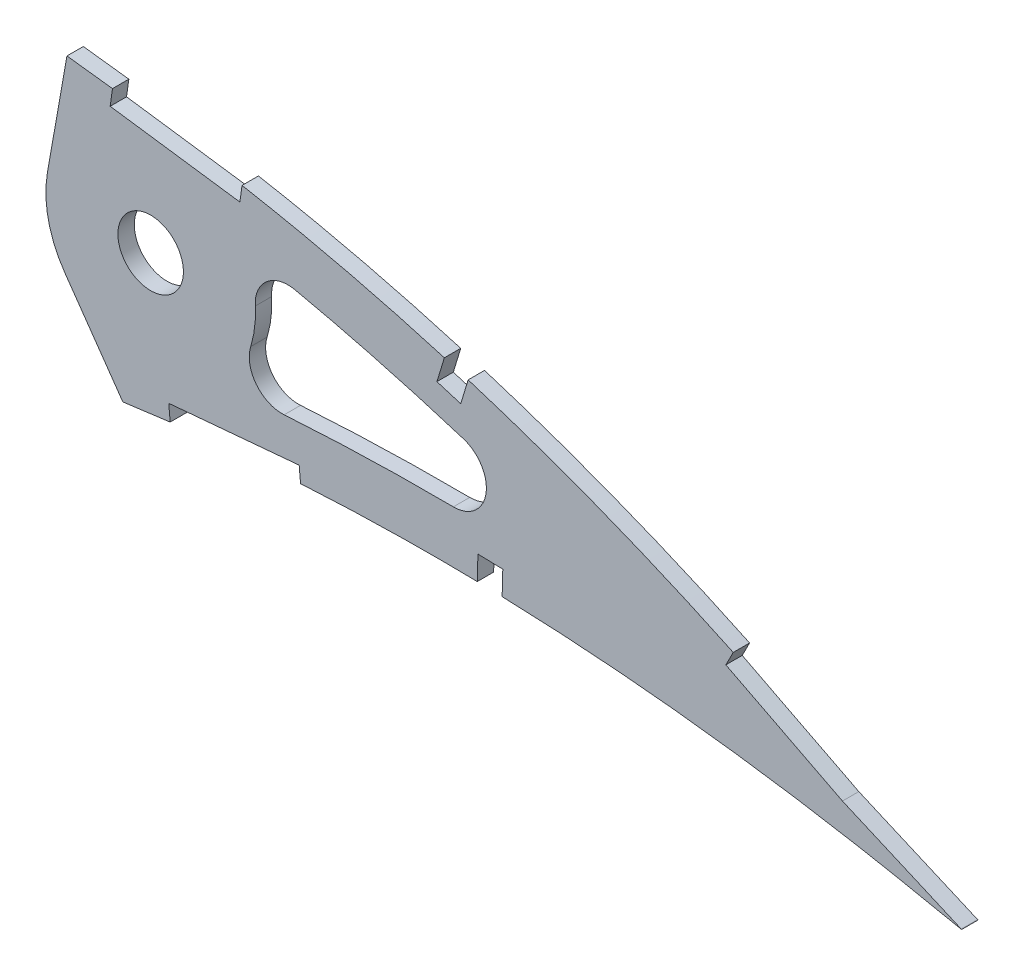
SolidWorks part; units mm, degrees
material "Pine"
ref_plane "Front Plane" through (0, 0, 0) normal (0, 0, 1) x (1, 0, 0)
ref_plane "Top Plane" through (0, 0, 0) normal (0, 1, 0) x (1, 0, 0)
ref_plane "Right Plane" through (0, 0, 0) normal (1, 0, 0) x (0, 0, -1)
curve "Curve2"
curve "Curve3"
sketch "Sketch1" plane through (0, 0, 0) normal (0, 0, 1) x (1, 0, 0)
  line L1 (519.5802, -0.8111) -> (524.4049, -1.7687)
  line L2 (520.229, 0.8111) -> (524.4049, -1.7687)
  spline S0 degree 3 poles (-2903.7635, -749.124) (66.2436, 68.8235) (-8.6937, 20.855) (1.129, -3.7148) (2.0912, -5.4642) (3.3081, -7.1386) (4.7718, -8.7374) (6.479, -10.2623) (8.428, -11.7125) (10.6162, -13.0874) (13.0406, -14.3883) (15.6982, -15.6145) (18.5868, -16.7656) (21.7032, -17.8401) (25.0435, -18.8396) (28.6046, -19.7616) (32.3825, -20.6074) (36.3735, -21.375) (40.5732, -22.065) (44.9774, -22.6771) (49.5814, -23.2117) (54.3808, -23.6676) (59.3708, -24.0458) (64.5464, -24.3466) (69.9027, -24.5709) (75.4344, -24.718) (81.1363, -24.7899) (87.003, -24.788) (93.0289, -24.7115) (99.2088, -24.5648) (105.5368, -24.3469) (112.0073, -24.0604) (118.6142, -23.7083) (125.3518, -23.2917) (132.2141, -22.8125) (139.1951, -22.2745) (146.2885, -21.679) (153.4882, -21.0296) (160.7876, -20.3295) (168.1806, -19.5808) (175.6606, -18.7872) (183.2209, -17.9512) (190.8551, -17.0772) (198.5563, -16.1668) (206.3179, -15.2253) (214.1326, -14.2544) (221.9939, -13.2579) (229.8947, -12.2404) (237.8276, -11.2019) (245.786, -10.1497) (253.7621, -9.0829) (261.7491, -8.0072) (269.7395, -6.9257) (277.7256, -5.8389) (285.7003, -4.7513) (293.6562, -3.6657) (301.5856, -2.5824) (309.4812, -1.5067) (317.3352, -0.4385) (325.1402, 0.6201) (332.8888, 1.6659) (340.5737, 2.6975) (348.187, 3.7144) (355.721, 4.7168) (363.0553, 5.6745) (370.1707, 6.6383) (377.0913, 7.4284) (383.9258, 8.1028) (390.6811, 8.6557) (397.3493, 9.0951) (403.9227, 9.4241) (410.3934, 9.6473) (416.7532, 9.7713) (422.9943, 9.7993) (429.1081, 9.7402) (435.0867, 9.5987) (440.9216, 9.3813) (446.6049, 9.0952) (452.1283, 8.7483) (457.4837, 8.3456) (462.6634, 7.8966) (467.6597, 7.4078) (472.4647, 6.8849) (477.0715, 6.3387) (481.4727, 5.7729) (485.6616, 5.1968) (489.6316, 4.6162) (493.3764, 4.0385) (496.89, 3.4693) (500.1667, 2.916) (503.2016, 2.384) (505.9892, 1.8782) (508.5257, 1.4052) (510.8062, 0.9673) (512.8275, 0.5717) (514.5859, 0.2202) (516.0789, -0.0824) (517.3037, -0.3347) (518.2586, -0.5328) (518.9417, -0.6767) (537.0698, -4.4604) (553.3394, -15.9066) (1193.1482, 2921.6684) knots -0.137857 -0.137857 -0.137857 -0.137857 0.003638 0.007293 0.011028 0.014901 0.018963 0.023258 0.027821 0.032679 0.037853 0.043362 0.049215 0.055422 0.061989 0.068918 0.076211 0.083868 0.091887 0.100266 0.109 0.118085 0.127515 0.137285 0.147388 0.157816 0.168563 0.179619 0.190977 0.202627 0.21456 0.226767 0.239236 0.251959 0.264924 0.27812 0.291536 0.30516 0.318981 0.332985 0.347163 0.361499 0.375981 0.390597 0.405333 0.420175 0.43511 0.450124 0.465203 0.480333 0.495501 0.51069 0.525887 0.541078 0.556247 0.571382 0.586466 0.601485 0.616424 0.631269 0.646007 0.660621 0.675098 0.689423 0.703582 0.716908 0.730009 0.742952 0.755726 0.76832 0.780724 0.792927 0.804916 0.816679 0.828204 0.839475 0.850481 0.861208 0.871639 0.881763 0.891564 0.901027 0.910139 0.918884 0.927249 0.935221 0.942785 0.949928 0.956638 0.962904 0.968712 0.974054 0.978918 0.983297 0.98718 0.990561 0.993433 0.995791 0.99763 0.998946 0.999737 1.102307 1.102307 1.102307 1.102307 only from (0, 0) to (519.5802, -0.8111) construction
  spline S1 degree 3 poles (2144.5607, 2521.6799) (550.9976, -26.3511) (537.2872, -9.6513) (519.6711, 1.1542) (519.0735, 1.5208) (518.237, 2.0313) (517.1622, 2.6844) (515.8486, 3.4756) (514.2969, 4.4021) (512.5075, 5.4598) (510.4807, 6.6436) (508.2172, 7.9486) (505.7172, 9.3676) (502.9816, 10.8948) (500.0114, 12.5227) (496.8072, 14.2443) (493.3701, 16.0505) (489.7015, 17.9338) (485.8019, 19.8836) (481.6733, 21.8919) (477.317, 23.9487) (472.7345, 26.0429) (467.9284, 28.1661) (462.9001, 30.305) (457.6524, 32.4505) (452.1876, 34.5902) (446.5089, 36.7144) (440.6184, 38.8094) (434.5207, 40.866) (428.2186, 42.8708) (421.7166, 44.813) (415.0186, 46.68) (408.1302, 48.4622) (401.0555, 50.1466) (393.8008, 51.7219) (386.3718, 53.1787) (378.7746, 54.5024) (371.0303, 55.692) (363.2636, 56.6815) (355.5128, 57.652) (347.7736, 58.5637) (339.9398, 59.4368) (332.019, 60.2663) (324.019, 61.0497) (315.9478, 61.7836) (307.814, 62.4658) (299.6253, 63.0925) (291.3904, 63.6628) (283.1174, 64.1714) (274.8152, 64.6183) (266.4922, 65.0001) (258.157, 65.3142) (249.8185, 65.5589) (241.4854, 65.7316) (233.1666, 65.8314) (224.8708, 65.8555) (216.6071, 65.8035) (208.384, 65.6736) (200.2107, 65.464) (192.0958, 65.1743) (184.048, 64.8046) (176.0762, 64.3519) (168.189, 63.8191) (160.3952, 63.2038) (152.7034, 62.506) (145.1216, 61.7286) (137.6583, 60.8693) (130.3214, 59.9308) (123.1191, 58.9147) (116.0593, 57.8206) (109.1496, 56.6517) (102.3976, 55.409) (95.8102, 54.0963) (89.3948, 52.714) (83.1581, 51.266) (77.1065, 49.7551) (71.2467, 48.1838) (65.5845, 46.5561) (60.1256, 44.8756) (54.8764, 43.1442) (49.8409, 41.3683) (45.0253, 39.5493) (40.4333, 37.6928) (36.0702, 35.8014) (31.9393, 33.8806) (28.0452, 31.9329) (24.3908, 29.9636) (20.9797, 27.9757) (17.8153, 25.973) (14.8987, 23.9604) (12.2341, 21.9394) (9.8224, 19.9149) (7.6651, 17.8901) (5.7652, 15.8664) (4.1228, 13.8473) (2.7399, 11.8344) (1.6168, 9.8297) (0.7561, 7.8345) (0.1568, 5.85) (-0.1712, 3.8792) (-1.2714, -22.5145) (85.5395, -42.7616) (-2987.8188, -259.5241) knots -0.109813 -0.109813 -0.109813 -0.109813 0.000254 0.001015 0.002283 0.004057 0.006331 0.009105 0.012374 0.016134 0.02038 0.025106 0.030306 0.035972 0.0421 0.048678 0.055702 0.06316 0.071046 0.07935 0.088063 0.097176 0.106678 0.116562 0.126814 0.137428 0.148394 0.1597 0.171338 0.183298 0.19557 0.208144 0.221012 0.234162 0.247587 0.261277 0.275223 0.289414 0.303771 0.317689 0.331784 0.34604 0.360444 0.374983 0.38964 0.404403 0.419257 0.434187 0.449177 0.464215 0.479284 0.49437 0.509458 0.524532 0.539579 0.554583 0.56953 0.584403 0.599191 0.613877 0.628447 0.642889 0.657186 0.671326 0.685294 0.699078 0.712665 0.726043 0.739198 0.752118 0.764792 0.777208 0.789356 0.801224 0.812804 0.824083 0.835055 0.84571 0.856038 0.866034 0.875689 0.884998 0.893953 0.902553 0.910789 0.918661 0.926166 0.933303 0.940071 0.946475 0.952518 0.958205 0.963547 0.968557 0.97325 0.977651 0.981787 0.985694 0.989415 0.993001 0.996508 1.132043 1.132043 1.132043 1.132043 only from (520.229, 0.8111) to (0, 0) construction
  spline S2 degree 3 poles (0, 0) (0.1336, -0.6306) (0.4014, -1.8948) (1.129, -3.7148) (2.0912, -5.4642) (3.3081, -7.1386) (4.7718, -8.7374) (6.479, -10.2623) (8.428, -11.7125) (10.6162, -13.0874) (13.0406, -14.3883) (15.6982, -15.6145) (18.5868, -16.7656) (21.7032, -17.8401) (25.0435, -18.8396) (28.6046, -19.7616) (32.3825, -20.6074) (36.3735, -21.375) (40.5732, -22.065) (44.9774, -22.6771) (49.5814, -23.2117) (54.3808, -23.6676) (59.3708, -24.0458) (64.5464, -24.3466) (69.9027, -24.5709) (75.4344, -24.718) (81.1363, -24.7899) (87.003, -24.788) (93.0289, -24.7115) (99.2088, -24.5648) (105.5368, -24.3469) (112.0073, -24.0604) (118.6142, -23.7083) (125.3518, -23.2917) (132.2141, -22.8125) (139.1951, -22.2745) (146.2885, -21.679) (153.4882, -21.0296) (160.7876, -20.3295) (168.1806, -19.5808) (175.6606, -18.7872) (183.2209, -17.9512) (190.8551, -17.0772) (198.5563, -16.1668) (206.3179, -15.2253) (214.1326, -14.2544) (221.9939, -13.2579) (229.8947, -12.2404) (237.8276, -11.2019) (245.786, -10.1497) (253.7621, -9.0829) (261.7491, -8.0072) (269.7395, -6.9257) (277.7256, -5.8389) (285.7003, -4.7513) (293.6562, -3.6657) (301.5856, -2.5824) (309.4812, -1.5067) (317.3352, -0.4385) (325.1402, 0.6201) (332.8888, 1.6659) (340.5737, 2.6975) (348.187, 3.7144) (355.721, 4.7168) (363.0553, 5.6745) (370.1707, 6.6383) (377.0913, 7.4284) (383.9258, 8.1028) (390.6811, 8.6557) (397.3493, 9.0951) (403.9227, 9.4241) (410.3934, 9.6473) (416.7532, 9.7713) (422.9943, 9.7993) (429.1081, 9.7402) (435.0867, 9.5987) (440.9216, 9.3813) (446.6049, 9.0952) (452.1283, 8.7483) (457.4837, 8.3456) (462.6634, 7.8966) (467.6597, 7.4078) (472.4647, 6.8849) (477.0715, 6.3387) (481.4727, 5.7729) (485.6616, 5.1968) (489.6316, 4.6162) (493.3764, 4.0385) (496.89, 3.4693) (500.1667, 2.916) (503.2016, 2.384) (505.9892, 1.8782) (508.5257, 1.4052) (510.8062, 0.9673) (512.8275, 0.5717) (514.5859, 0.2202) (516.0789, -0.0824) (517.3037, -0.3347) (518.2586, -0.5328) (518.9417, -0.6767) (519.3522, -0.7624) (519.5346, -0.8013) (519.5802, -0.8111) knots 0 0 0 0 0.003638 0.007293 0.011028 0.014901 0.018963 0.023258 0.027821 0.032679 0.037853 0.043362 0.049215 0.055422 0.061989 0.068918 0.076211 0.083868 0.091887 0.100266 0.109 0.118085 0.127515 0.137285 0.147388 0.157816 0.168563 0.179619 0.190977 0.202627 0.21456 0.226767 0.239236 0.251959 0.264924 0.27812 0.291536 0.30516 0.318981 0.332985 0.347163 0.361499 0.375981 0.390597 0.405333 0.420175 0.43511 0.450124 0.465203 0.480333 0.495501 0.51069 0.525887 0.541078 0.556247 0.571382 0.586466 0.601485 0.616424 0.631269 0.646007 0.660621 0.675098 0.689423 0.703582 0.716908 0.730009 0.742952 0.755726 0.76832 0.780724 0.792927 0.804916 0.816679 0.828204 0.839475 0.850481 0.861208 0.871639 0.881763 0.891564 0.901027 0.910139 0.918884 0.927249 0.935221 0.942785 0.949928 0.956638 0.962904 0.968712 0.974054 0.978918 0.983297 0.98718 0.990561 0.993433 0.995791 0.99763 0.998946 0.999737 1 1 1 1
  spline S3 degree 3 poles (520.229, 0.8111) (520.1892, 0.8357) (520.0299, 0.9341) (519.6711, 1.1542) (519.0735, 1.5208) (518.237, 2.0313) (517.1622, 2.6844) (515.8486, 3.4756) (514.2969, 4.4021) (512.5075, 5.4598) (510.4807, 6.6436) (508.2172, 7.9486) (505.7172, 9.3676) (502.9816, 10.8948) (500.0114, 12.5227) (496.8072, 14.2443) (493.3701, 16.0505) (489.7015, 17.9338) (485.8019, 19.8836) (481.6733, 21.8919) (477.317, 23.9487) (472.7345, 26.0429) (467.9284, 28.1661) (462.9001, 30.305) (457.6524, 32.4505) (452.1876, 34.5902) (446.5089, 36.7144) (440.6184, 38.8094) (434.5207, 40.866) (428.2186, 42.8708) (421.7166, 44.813) (415.0186, 46.68) (408.1302, 48.4622) (401.0555, 50.1466) (393.8008, 51.7219) (386.3718, 53.1787) (378.7746, 54.5024) (371.0303, 55.692) (363.2636, 56.6815) (355.5128, 57.652) (347.7736, 58.5637) (339.9398, 59.4368) (332.019, 60.2663) (324.019, 61.0497) (315.9478, 61.7836) (307.814, 62.4658) (299.6253, 63.0925) (291.3904, 63.6628) (283.1174, 64.1714) (274.8152, 64.6183) (266.4922, 65.0001) (258.157, 65.3142) (249.8185, 65.5589) (241.4854, 65.7316) (233.1666, 65.8314) (224.8708, 65.8555) (216.6071, 65.8035) (208.384, 65.6736) (200.2107, 65.464) (192.0958, 65.1743) (184.048, 64.8046) (176.0762, 64.3519) (168.189, 63.8191) (160.3952, 63.2038) (152.7034, 62.506) (145.1216, 61.7286) (137.6583, 60.8693) (130.3214, 59.9308) (123.1191, 58.9147) (116.0593, 57.8206) (109.1496, 56.6517) (102.3976, 55.409) (95.8102, 54.0963) (89.3948, 52.714) (83.1581, 51.266) (77.1065, 49.7551) (71.2467, 48.1838) (65.5845, 46.5561) (60.1256, 44.8756) (54.8764, 43.1442) (49.8409, 41.3683) (45.0253, 39.5493) (40.4333, 37.6928) (36.0702, 35.8014) (31.9393, 33.8806) (28.0452, 31.9329) (24.3908, 29.9636) (20.9797, 27.9757) (17.8153, 25.973) (14.8987, 23.9604) (12.2341, 21.9394) (9.8224, 19.9149) (7.6651, 17.8901) (5.7652, 15.8664) (4.1228, 13.8473) (2.7399, 11.8344) (1.6168, 9.8297) (0.7561, 7.8345) (0.1568, 5.85) (-0.1712, 3.8792) (-0.2528, 1.9205) (-0.0842, 0.6392) (0, 0) knots 0 0 0 0 0.000254 0.001015 0.002283 0.004057 0.006331 0.009105 0.012374 0.016134 0.02038 0.025106 0.030306 0.035972 0.0421 0.048678 0.055702 0.06316 0.071046 0.07935 0.088063 0.097176 0.106678 0.116562 0.126814 0.137428 0.148394 0.1597 0.171338 0.183298 0.19557 0.208144 0.221012 0.234162 0.247587 0.261277 0.275223 0.289414 0.303771 0.317689 0.331784 0.34604 0.360444 0.374983 0.38964 0.404403 0.419257 0.434187 0.449177 0.464215 0.479284 0.49437 0.509458 0.524532 0.539579 0.554583 0.56953 0.584403 0.599191 0.613877 0.628447 0.642889 0.657186 0.671326 0.685294 0.699078 0.712665 0.726043 0.739198 0.752118 0.764792 0.777208 0.789356 0.801224 0.812804 0.824083 0.835055 0.84571 0.856038 0.866034 0.875689 0.884998 0.893953 0.902553 0.910789 0.918661 0.926166 0.933303 0.940071 0.946475 0.952518 0.958205 0.963547 0.968557 0.97325 0.977651 0.981787 0.985694 0.989415 0.993001 0.996508 1 1 1 1
extrude "Boss-Extrude1" add sketch "Sketch1" along normal blind 3.175
sketch "Sketch4" plane through (0, 0, 0) normal (0, 0, -1) x (-1, 0, 0)
  line L0 (-347.1309, 36.7611) -> (-350.9097, 58.1919)
  line L1 (-350.497, 21.5775) -> (-361.7496, 5.5072)
  line L2 (-367.1422, 33.2326) -> (-406.863, 33.2326)
  circle A0 centre (-367.1422, 33.2326) radius 20.32
  circle A1 centre (-367.1422, 33.2326) radius 6.35
  spline S2 degree 3 poles (1939.7558, -484.7932) (-49.4812, 57.6608) (7.5449, 17.9816) (-1.129, -3.7148) (-2.0912, -5.4642) (-3.3081, -7.1386) (-4.7718, -8.7374) (-6.479, -10.2623) (-8.428, -11.7125) (-10.6162, -13.0874) (-13.0406, -14.3883) (-15.6982, -15.6145) (-18.5868, -16.7656) (-21.7032, -17.8401) (-25.0435, -18.8396) (-28.6046, -19.7616) (-32.3825, -20.6074) (-36.3735, -21.375) (-40.5732, -22.065) (-44.9774, -22.6771) (-49.5814, -23.2117) (-54.3808, -23.6676) (-59.3708, -24.0458) (-64.5464, -24.3466) (-69.9027, -24.5709) (-75.4344, -24.718) (-81.1363, -24.7899) (-87.003, -24.788) (-93.0289, -24.7115) (-99.2088, -24.5648) (-105.5368, -24.3469) (-112.0073, -24.0604) (-118.6142, -23.7083) (-125.3518, -23.2917) (-132.2141, -22.8125) (-139.1951, -22.2745) (-146.2885, -21.679) (-153.4882, -21.0296) (-160.7876, -20.3295) (-168.1806, -19.5808) (-175.6606, -18.7872) (-183.2209, -17.9512) (-190.8551, -17.0772) (-198.5563, -16.1668) (-206.3179, -15.2253) (-214.1326, -14.2544) (-221.9939, -13.2579) (-229.8947, -12.2404) (-237.8276, -11.2019) (-245.786, -10.1497) (-253.7621, -9.0829) (-261.7491, -8.0072) (-269.7395, -6.9257) (-277.7256, -5.8389) (-285.7003, -4.7513) (-293.6562, -3.6657) (-301.5856, -2.5824) (-309.4812, -1.5067) (-317.3352, -0.4385) (-325.1402, 0.6201) (-332.8888, 1.6659) (-340.5737, 2.6975) (-348.187, 3.7144) (-355.721, 4.7168) (-363.0553, 5.6745) (-370.1707, 6.6383) (-377.0913, 7.4284) (-383.9258, 8.1028) (-390.6811, 8.6557) (-397.3493, 9.0951) (-403.9227, 9.4241) (-410.3934, 9.6473) (-416.7532, 9.7713) (-422.9943, 9.7993) (-429.1081, 9.7402) (-435.0867, 9.5987) (-440.9216, 9.3813) (-446.6049, 9.0952) (-452.1283, 8.7483) (-457.4837, 8.3456) (-462.6634, 7.8966) (-467.6597, 7.4078) (-472.4647, 6.8849) (-477.0715, 6.3387) (-481.4727, 5.7729) (-485.6616, 5.1968) (-489.6316, 4.6162) (-493.3764, 4.0385) (-496.89, 3.4693) (-500.1667, 2.916) (-503.2016, 2.384) (-505.9892, 1.8782) (-508.5257, 1.4052) (-510.8062, 0.9673) (-512.8275, 0.5717) (-514.5859, 0.2202) (-516.0789, -0.0824) (-517.3037, -0.3347) (-518.2586, -0.5328) (-518.9417, -0.6767) (-534.8295, -3.9928) (-549.2415, -13.1623) (-979.5797, 1945.0117) knots -0.120445 -0.120445 -0.120445 -0.120445 0.003638 0.007293 0.011028 0.014901 0.018963 0.023258 0.027821 0.032679 0.037853 0.043362 0.049215 0.055422 0.061989 0.068918 0.076211 0.083868 0.091887 0.100266 0.109 0.118085 0.127515 0.137285 0.147388 0.157816 0.168563 0.179619 0.190977 0.202627 0.21456 0.226767 0.239236 0.251959 0.264924 0.27812 0.291536 0.30516 0.318981 0.332985 0.347163 0.361499 0.375981 0.390597 0.405333 0.420175 0.43511 0.450124 0.465203 0.480333 0.495501 0.51069 0.525887 0.541078 0.556247 0.571382 0.586466 0.601485 0.616424 0.631269 0.646007 0.660621 0.675098 0.689423 0.703582 0.716908 0.730009 0.742952 0.755726 0.76832 0.780724 0.792927 0.804916 0.816679 0.828204 0.839475 0.850481 0.861208 0.871639 0.881763 0.891564 0.901027 0.910139 0.918884 0.927249 0.935221 0.942785 0.949928 0.956638 0.962904 0.968712 0.974054 0.978918 0.983297 0.98718 0.990561 0.993433 0.995791 0.99763 0.998946 0.999737 1.089371 1.089371 1.089371 1.089371 only from (0, 0) to (-519.5802, -0.8111) construction
  spline S3 degree 3 poles (-1613.7482, 1674.6901) (-547.5042, -22.2613) (-535.1053, -8.313) (-519.6711, 1.1542) (-519.0735, 1.5208) (-518.237, 2.0313) (-517.1622, 2.6844) (-515.8486, 3.4756) (-514.2969, 4.4021) (-512.5075, 5.4598) (-510.4807, 6.6436) (-508.2172, 7.9486) (-505.7172, 9.3676) (-502.9816, 10.8948) (-500.0114, 12.5227) (-496.8072, 14.2443) (-493.3701, 16.0505) (-489.7015, 17.9338) (-485.8019, 19.8836) (-481.6733, 21.8919) (-477.317, 23.9487) (-472.7345, 26.0429) (-467.9284, 28.1661) (-462.9001, 30.305) (-457.6524, 32.4505) (-452.1876, 34.5902) (-446.5089, 36.7144) (-440.6184, 38.8094) (-434.5207, 40.866) (-428.2186, 42.8708) (-421.7166, 44.813) (-415.0186, 46.68) (-408.1302, 48.4622) (-401.0555, 50.1466) (-393.8008, 51.7219) (-386.3718, 53.1787) (-378.7746, 54.5024) (-371.0303, 55.692) (-363.2636, 56.6815) (-355.5128, 57.652) (-347.7736, 58.5637) (-339.9398, 59.4368) (-332.019, 60.2663) (-324.019, 61.0497) (-315.9478, 61.7836) (-307.814, 62.4658) (-299.6253, 63.0925) (-291.3904, 63.6628) (-283.1174, 64.1714) (-274.8152, 64.6183) (-266.4922, 65.0001) (-258.157, 65.3142) (-249.8185, 65.5589) (-241.4854, 65.7316) (-233.1666, 65.8314) (-224.8708, 65.8555) (-216.6071, 65.8035) (-208.384, 65.6736) (-200.2107, 65.464) (-192.0958, 65.1743) (-184.048, 64.8046) (-176.0762, 64.3519) (-168.189, 63.8191) (-160.3952, 63.2038) (-152.7034, 62.506) (-145.1216, 61.7286) (-137.6583, 60.8693) (-130.3214, 59.9308) (-123.1191, 58.9147) (-116.0593, 57.8206) (-109.1496, 56.6517) (-102.3976, 55.409) (-95.8102, 54.0963) (-89.3948, 52.714) (-83.1581, 51.266) (-77.1065, 49.7551) (-71.2467, 48.1838) (-65.5845, 46.5561) (-60.1256, 44.8756) (-54.8764, 43.1442) (-49.8409, 41.3683) (-45.0253, 39.5493) (-40.4333, 37.6928) (-36.0702, 35.8014) (-31.9393, 33.8806) (-28.0452, 31.9329) (-24.3908, 29.9636) (-20.9797, 27.9757) (-17.8153, 25.973) (-14.8987, 23.9604) (-12.2341, 21.9394) (-9.8224, 19.9149) (-7.6651, 17.8901) (-5.7652, 15.8664) (-4.1228, 13.8473) (-2.7399, 11.8344) (-1.6168, 9.8297) (-0.7561, 7.8345) (-0.1568, 5.85) (0.1712, 3.8792) (1.1427, -19.4272) (-65.9725, -37.8239) (1990.4087, -188.0581) knots -0.095928 -0.095928 -0.095928 -0.095928 0.000254 0.001015 0.002283 0.004057 0.006331 0.009105 0.012374 0.016134 0.02038 0.025106 0.030306 0.035972 0.0421 0.048678 0.055702 0.06316 0.071046 0.07935 0.088063 0.097176 0.106678 0.116562 0.126814 0.137428 0.148394 0.1597 0.171338 0.183298 0.19557 0.208144 0.221012 0.234162 0.247587 0.261277 0.275223 0.289414 0.303771 0.317689 0.331784 0.34604 0.360444 0.374983 0.38964 0.404403 0.419257 0.434187 0.449177 0.464215 0.479284 0.49437 0.509458 0.524532 0.539579 0.554583 0.56953 0.584403 0.599191 0.613877 0.628447 0.642889 0.657186 0.671326 0.685294 0.699078 0.712665 0.726043 0.739198 0.752118 0.764792 0.777208 0.789356 0.801224 0.812804 0.824083 0.835055 0.84571 0.856038 0.866034 0.875689 0.884998 0.893953 0.902553 0.910789 0.918661 0.926166 0.933303 0.940071 0.946475 0.952518 0.958205 0.963547 0.968557 0.97325 0.977651 0.981787 0.985694 0.989415 0.993001 0.996508 1.11536 1.11536 1.11536 1.11536 only from (-520.229, 0.8111) to (0, 0) construction
  spline S4 degree 3 poles (-1978.354, 2157.5892) (159.6529, 858.6126) (-7.0413, 13.2519) (-10.1565, 1.1414) (-10.167, 1.1042) (-10.1763, 1.0725) (-10.1781, 1.0668) (-10.1835, 1.0497) (-10.1867, 1.0399) (-10.2052, 0.985) (-10.2286, 0.9219) (-10.2791, 0.8017) (-10.2985, 0.7574) (-10.3426, 0.661) (-10.3676, 0.6085) (-10.4428, 0.4561) (-10.496, 0.3558) (-10.6081, 0.1584) (-10.6662, 0.0627) (-10.855, -0.2291) (-11.0064, -0.4384) (-11.5378, -1.0936) (-11.9971, -1.5677) (-13.099, -2.5256) (-13.7412, -3.01) (-15.1702, -3.9568) (-15.9588, -4.4208) (-17.636, -5.3094) (-18.5262, -5.7351) (-21.3094, -6.9503) (-23.3073, -7.6749) (-27.467, -8.9758) (-29.6229, -9.5497) (-34.0316, -10.5753) (-36.2795, -11.0252) (-40.839, -11.8243) (-43.1471, -12.1728) (-47.8035, -12.7862) (-50.1501, -13.0508) (-57.2292, -13.7373) (-62.003, -14.0541) (-71.5985, -14.4809) (-76.422, -14.5891) (-83.6816, -14.6324) (-86.1037, -14.6268) (-90.9551, -14.5789) (-93.3856, -14.5371) (-100.6793, -14.3647) (-105.548, -14.1854) (-120.1773, -13.4939) (-129.9476, -12.83) (-149.5009, -11.2301) (-159.287, -10.2936) (-178.863, -8.2392) (-188.6532, -7.1203) (-203.3458, -5.3542) (-208.2424, -4.7511) (-218.0387, -3.5207) (-222.9395, -2.8943) (-232.7359, -1.6243) (-237.6385, -0.9795) (-247.4393, 0.3202) (-252.3404, 0.9774) (-262.147, 2.2986) (-267.05, 2.9625) (-276.8577, 4.2964) (-281.7641, 4.9659) (-291.5768, 6.3047) (-296.4825, 6.9752) (-306.3007, 8.3142) (-311.2087, 8.9822) (-325.9378, 10.9826) (-335.766, 12.3068) (-348.0467, 13.9451) (-350.5039, 14.2725) (-354.1964, 14.7609) (-355.4285, 14.923) (-357.8843, 15.2457) (-359.1092, 15.4066) (-361.5526, 15.7296) (-362.7689, 15.8922) (-365.2348, 16.221) (-366.4798, 16.3859) (-368.3663, 16.6273) (-368.9995, 16.7068) (-371.53, 17.0174) (-373.424, 17.2342) (-377.8329, 17.7104) (-380.3527, 17.9617) (-385.4072, 18.4196) (-387.9354, 18.6255) (-395.5221, 19.1767) (-400.5883, 19.4552) (-408.19, 19.7386) (-410.7237, 19.8108) (-415.7936, 19.9113) (-418.3301, 19.9392) (-425.9339, 19.9566) (-431.0019, 19.8815) (-441.1324, 19.5579) (-446.1907, 19.3102) (-453.7725, 18.8139) (-456.2982, 18.6271) (-775.6257, -7.5609) (-1062.3017, -351.5368) (-2984.1092, -1609.9578) knots -0.216436 -0.216436 -0.216436 -0.216436 0.001953 0.001953 0.00293 0.00293 0.003418 0.003418 0.003906 0.003906 0.005859 0.005859 0.006836 0.006836 0.007813 0.007813 0.009766 0.009766 0.011719 0.011719 0.015625 0.015625 0.023438 0.023438 0.03125 0.03125 0.039063 0.039063 0.046875 0.046875 0.0625 0.0625 0.078125 0.078125 0.09375 0.09375 0.109375 0.109375 0.125 0.125 0.15625 0.15625 0.1875 0.1875 0.203125 0.203125 0.21875 0.21875 0.25 0.25 0.3125 0.3125 0.375 0.375 0.4375 0.4375 0.46875 0.46875 0.5 0.5 0.53125 0.53125 0.5625 0.5625 0.59375 0.59375 0.625 0.625 0.65625 0.65625 0.6875 0.6875 0.75 0.75 0.765625 0.765625 0.773438 0.773438 0.78125 0.78125 0.789063 0.789063 0.796875 0.796875 0.800781 0.800781 0.8125 0.8125 0.828125 0.828125 0.84375 0.84375 0.875 0.875 0.890625 0.890625 0.90625 0.90625 0.9375 0.9375 0.96875 0.96875 0.984375 0.984375 2.947098 2.947098 2.947098 2.947098 only from (-10.022, 1.7185) to (-466.3815, 17.739)
  spline S5 degree 3 poles (-2960.1923, -1647.6146) (-778.0163, -316.2747) (-661.2066, -63.7231) (-457.1185, 21.6971) (-454.7864, 22.6463) (-450.1039, 24.4978) (-447.7524, 25.4007) (-443.0352, 27.1579) (-440.669, 28.0121) (-428.7885, 32.1652) (-419.1573, 35.0991) (-404.5516, 38.8923) (-399.6593, 40.0545) (-392.2853, 41.6432) (-389.8214, 42.1473) (-384.8862, 43.1026) (-382.4148, 43.5535) (-377.456, 44.4051) (-374.9691, 44.8071) (-371.8706, 45.272) (-371.2512, 45.3631) (-370.0129, 45.5414) (-369.3949, 45.6283) (-367.531, 45.885) (-365.6514, 46.1331) (-363.7495, 46.3759) (-362.4766, 46.5374) (-361.8369, 46.6182) (-359.9197, 46.8599) (-358.6437, 47.0199) (-354.8218, 47.4941) (-352.2828, 47.8012) (-347.1922, 48.3982) (-344.6438, 48.6888) (-339.5477, 49.2537) (-336.9993, 49.5279) (-329.3512, 50.3256) (-324.2496, 50.8242) (-308.9368, 52.2174) (-298.7176, 53.0107) (-278.2717, 54.3039) (-268.0406, 54.8057) (-247.5801, 55.4913) (-237.3501, 55.6755) (-216.9004, 55.6922) (-206.6831, 55.5256) (-191.3779, 54.9785) (-186.2812, 54.7472) (-176.0979, 54.177) (-171.0099, 53.8396) (-160.8533, 53.0504) (-155.7814, 52.598) (-145.6574, 51.572) (-140.6072, 50.9971) (-125.4892, 49.071) (-115.4646, 47.5214) (-100.5547, 44.7064) (-95.6096, 43.687) (-85.777, 41.462) (-80.8922, 40.2578) (-71.2072, 37.6367) (-66.4068, 36.2209) (-59.3024, 33.909) (-56.9474, 33.1063) (-52.2821, 31.4343) (-49.9693, 30.5636) (-45.3927, 28.7458) (-43.1318, 27.7996) (-38.6715, 25.8196) (-36.476, 24.7882) (-32.1758, 22.6281) (-30.0692, 21.4995) (-27.0125, 19.7284) (-26.0103, 19.1247) (-24.0464, 17.889) (-23.0831, 17.2561) (-21.2128, 15.9659) (-20.3049, 15.3076) (-18.5534, 13.9629) (-17.7093, 13.2763) (-16.1081, 11.8824) (-15.3519, 11.176) (-14.3045, 10.1109) (-13.9701, 9.7552) (-13.3325, 9.0431) (-13.0296, 8.687) (-12.1803, 7.6299) (-11.6896, 6.9348) (-10.8906, 5.6128) (-10.5874, 4.9936) (-10.269, 4.158) (-10.1861, 3.8969) (-10.0953, 3.5459) (-10.0707, 3.4366) (-10.0267, 3.2104) (-10.0081, 3.096) (-9.9777, 2.8649) (-9.9658, 2.7438) (-9.9529, 2.5547) (-9.9512, 2.4811) (-9.9516, 2.4178) (-9.9518, 2.4066) (-9.9523, 2.387) (-9.9526, 2.38) (-9.9538, 2.3538) (-9.956, 2.318) (-10.9137, -8.9231) (-124.2495, -805.3826) (-2616.8841, -1329.8892) knots -1.341255 -1.341255 -1.341255 -1.341255 0.015625 0.015625 0.03125 0.03125 0.046875 0.046875 0.0625 0.0625 0.125 0.125 0.15625 0.15625 0.171875 0.171875 0.1875 0.1875 0.203125 0.203125 0.207031 0.207031 0.210937 0.210937 0.21875 0.222656 0.222656 0.226562 0.226562 0.234375 0.234375 0.25 0.25 0.265625 0.265625 0.28125 0.28125 0.3125 0.3125 0.375 0.375 0.4375 0.4375 0.5 0.5 0.5625 0.5625 0.59375 0.59375 0.625 0.625 0.65625 0.65625 0.6875 0.6875 0.75 0.75 0.78125 0.78125 0.8125 0.8125 0.84375 0.84375 0.859375 0.859375 0.875 0.875 0.890625 0.890625 0.90625 0.90625 0.921875 0.921875 0.929688 0.929688 0.9375 0.9375 0.945313 0.945313 0.953125 0.953125 0.960938 0.960938 0.964844 0.964844 0.96875 0.96875 0.976563 0.976563 0.984375 0.984375 0.988281 0.988281 0.990234 0.990234 0.992188 0.992188 0.994141 0.994141 0.996094 0.996094 0.996582 0.996582 0.99707 0.99707 0.998047 0.998047 1.199641 1.199641 1.199641 1.199641 only from (-466.3815, 17.739) to (-10.022, 1.7185)
  spline S6 degree 3 poles (-10.022, 1.7185) (-10.0741, 1.4777) (-10.1149, 1.3032) (-10.1565, 1.1414) (-10.167, 1.1042) (-10.1763, 1.0725) (-10.1781, 1.0668) (-10.1835, 1.0497) (-10.1867, 1.0399) (-10.2052, 0.985) (-10.2286, 0.9219) (-10.2791, 0.8017) (-10.2985, 0.7574) (-10.3426, 0.661) (-10.3676, 0.6085) (-10.4428, 0.4561) (-10.496, 0.3558) (-10.6081, 0.1584) (-10.6662, 0.0627) (-10.855, -0.2291) (-11.0064, -0.4384) (-11.5378, -1.0936) (-11.9971, -1.5677) (-13.099, -2.5256) (-13.7412, -3.01) (-15.1702, -3.9568) (-15.9588, -4.4208) (-17.636, -5.3094) (-18.5262, -5.7351) (-21.3094, -6.9503) (-23.3073, -7.6749) (-27.467, -8.9758) (-29.6229, -9.5497) (-34.0316, -10.5753) (-36.2795, -11.0252) (-40.839, -11.8243) (-43.1471, -12.1728) (-47.8035, -12.7862) (-50.1501, -13.0508) (-57.2292, -13.7373) (-62.003, -14.0541) (-71.5985, -14.4809) (-76.422, -14.5891) (-83.6816, -14.6324) (-86.1037, -14.6268) (-90.9551, -14.5789) (-93.3856, -14.5371) (-100.6793, -14.3647) (-105.548, -14.1854) (-120.1773, -13.4939) (-129.9476, -12.83) (-149.5009, -11.2301) (-159.287, -10.2936) (-178.863, -8.2392) (-188.6532, -7.1203) (-203.3458, -5.3542) (-208.2424, -4.7511) (-218.0387, -3.5207) (-222.9395, -2.8943) (-232.7359, -1.6243) (-237.6385, -0.9795) (-247.4393, 0.3202) (-252.3404, 0.9774) (-262.147, 2.2986) (-267.05, 2.9625) (-276.8577, 4.2964) (-281.7641, 4.9659) (-291.5768, 6.3047) (-296.4825, 6.9752) (-306.3007, 8.3142) (-311.2087, 8.9822) (-325.9378, 10.9826) (-335.766, 12.3068) (-348.0467, 13.9451) (-350.5039, 14.2725) (-354.1964, 14.7609) (-355.4285, 14.923) (-357.8843, 15.2457) (-359.1092, 15.4066) (-361.5526, 15.7296) (-362.7689, 15.8922) (-365.2348, 16.221) (-366.4798, 16.3859) (-368.3663, 16.6273) (-368.9995, 16.7068) (-371.53, 17.0174) (-373.424, 17.2342) (-377.8329, 17.7104) (-380.3527, 17.9617) (-385.4072, 18.4196) (-387.9354, 18.6255) (-395.5221, 19.1767) (-400.5883, 19.4552) (-408.19, 19.7386) (-410.7237, 19.8108) (-415.7936, 19.9113) (-418.3301, 19.9392) (-425.9339, 19.9566) (-431.0019, 19.8815) (-441.1324, 19.5579) (-446.1907, 19.3102) (-453.7725, 18.8139) (-456.2982, 18.6271) (-461.3423, 18.2134) (-463.8625, 17.9865) (-466.3815, 17.739) knots 0 0 0 0 0.001953 0.001953 0.00293 0.00293 0.003418 0.003418 0.003906 0.003906 0.005859 0.005859 0.006836 0.006836 0.007813 0.007813 0.009766 0.009766 0.011719 0.011719 0.015625 0.015625 0.023438 0.023438 0.03125 0.03125 0.039063 0.039063 0.046875 0.046875 0.0625 0.0625 0.078125 0.078125 0.09375 0.09375 0.109375 0.109375 0.125 0.125 0.15625 0.15625 0.1875 0.1875 0.203125 0.203125 0.21875 0.21875 0.25 0.25 0.3125 0.3125 0.375 0.375 0.4375 0.4375 0.46875 0.46875 0.5 0.5 0.53125 0.53125 0.5625 0.5625 0.59375 0.59375 0.625 0.625 0.65625 0.65625 0.6875 0.6875 0.75 0.75 0.765625 0.765625 0.773438 0.773438 0.78125 0.78125 0.789063 0.789063 0.796875 0.796875 0.800781 0.800781 0.8125 0.8125 0.828125 0.828125 0.84375 0.84375 0.875 0.875 0.890625 0.890625 0.90625 0.90625 0.9375 0.9375 0.96875 0.96875 0.984375 0.984375 1 1 1 1
  spline S7 degree 3 poles (-466.3815, 17.739) (-464.0774, 18.7574) (-461.7652, 19.7522) (-457.1185, 21.6971) (-454.7864, 22.6463) (-450.1039, 24.4978) (-447.7524, 25.4007) (-443.0352, 27.1579) (-440.669, 28.0121) (-428.7885, 32.1652) (-419.1573, 35.0991) (-404.5516, 38.8923) (-399.6593, 40.0545) (-392.2853, 41.6432) (-389.8214, 42.1473) (-384.8862, 43.1026) (-382.4148, 43.5535) (-377.456, 44.4051) (-374.9691, 44.8071) (-371.8706, 45.272) (-371.2512, 45.3631) (-370.0129, 45.5414) (-369.3949, 45.6283) (-367.531, 45.885) (-365.6514, 46.1331) (-363.7495, 46.3759) (-362.4766, 46.5374) (-361.8369, 46.6182) (-359.9197, 46.8599) (-358.6437, 47.0199) (-354.8218, 47.4941) (-352.2828, 47.8012) (-347.1922, 48.3982) (-344.6438, 48.6888) (-339.5477, 49.2537) (-336.9993, 49.5279) (-329.3512, 50.3256) (-324.2496, 50.8242) (-308.9368, 52.2174) (-298.7176, 53.0107) (-278.2717, 54.3039) (-268.0406, 54.8057) (-247.5801, 55.4913) (-237.3501, 55.6755) (-216.9004, 55.6922) (-206.6831, 55.5256) (-191.3779, 54.9785) (-186.2812, 54.7472) (-176.0979, 54.177) (-171.0099, 53.8396) (-160.8533, 53.0504) (-155.7814, 52.598) (-145.6574, 51.572) (-140.6072, 50.9971) (-125.4892, 49.071) (-115.4646, 47.5214) (-100.5547, 44.7064) (-95.6096, 43.687) (-85.777, 41.462) (-80.8922, 40.2578) (-71.2072, 37.6367) (-66.4068, 36.2209) (-59.3024, 33.909) (-56.9474, 33.1063) (-52.2821, 31.4343) (-49.9693, 30.5636) (-45.3927, 28.7458) (-43.1318, 27.7996) (-38.6715, 25.8196) (-36.476, 24.7882) (-32.1758, 22.6281) (-30.0692, 21.4995) (-27.0125, 19.7284) (-26.0103, 19.1247) (-24.0464, 17.889) (-23.0831, 17.2561) (-21.2128, 15.9659) (-20.3049, 15.3076) (-18.5534, 13.9629) (-17.7093, 13.2763) (-16.1081, 11.8824) (-15.3519, 11.176) (-14.3045, 10.1109) (-13.9701, 9.7552) (-13.3325, 9.0431) (-13.0296, 8.687) (-12.1803, 7.6299) (-11.6896, 6.9348) (-10.8906, 5.6128) (-10.5874, 4.9936) (-10.269, 4.158) (-10.1861, 3.8969) (-10.0953, 3.5459) (-10.0707, 3.4366) (-10.0267, 3.2104) (-10.0081, 3.096) (-9.9777, 2.8649) (-9.9658, 2.7438) (-9.9529, 2.5547) (-9.9512, 2.4811) (-9.9516, 2.4178) (-9.9518, 2.4066) (-9.9523, 2.387) (-9.9526, 2.38) (-9.9538, 2.3538) (-9.956, 2.318) (-9.9698, 2.1554) (-9.9896, 1.9733) (-10.022, 1.7185) knots 0 0 0 0 0.015625 0.015625 0.03125 0.03125 0.046875 0.046875 0.0625 0.0625 0.125 0.125 0.15625 0.15625 0.171875 0.171875 0.1875 0.1875 0.203125 0.203125 0.207031 0.207031 0.210937 0.210937 0.21875 0.222656 0.222656 0.226562 0.226562 0.234375 0.234375 0.25 0.25 0.265625 0.265625 0.28125 0.28125 0.3125 0.3125 0.375 0.375 0.4375 0.4375 0.5 0.5 0.5625 0.5625 0.59375 0.59375 0.625 0.625 0.65625 0.65625 0.6875 0.6875 0.75 0.75 0.78125 0.78125 0.8125 0.8125 0.84375 0.84375 0.859375 0.859375 0.875 0.875 0.890625 0.890625 0.90625 0.90625 0.921875 0.921875 0.929688 0.929688 0.9375 0.9375 0.945313 0.945313 0.953125 0.953125 0.960938 0.960938 0.964844 0.964844 0.96875 0.96875 0.976563 0.976563 0.984375 0.984375 0.988281 0.988281 0.990234 0.990234 0.992188 0.992188 0.994141 0.994141 0.996094 0.996094 0.996582 0.996582 0.99707 0.99707 0.998047 0.998047 1 1 1 1
  spline S8 degree 3 poles (0, 0) (-0.1336, -0.6306) (-0.4014, -1.8948) (-1.129, -3.7148) (-2.0912, -5.4642) (-3.3081, -7.1386) (-4.7718, -8.7374) (-6.479, -10.2623) (-8.428, -11.7125) (-10.6162, -13.0874) (-13.0406, -14.3883) (-15.6982, -15.6145) (-18.5868, -16.7656) (-21.7032, -17.8401) (-25.0435, -18.8396) (-28.6046, -19.7616) (-32.3825, -20.6074) (-36.3735, -21.375) (-40.5732, -22.065) (-44.9774, -22.6771) (-49.5814, -23.2117) (-54.3808, -23.6676) (-59.3708, -24.0458) (-64.5464, -24.3466) (-69.9027, -24.5709) (-75.4344, -24.718) (-81.1363, -24.7899) (-87.003, -24.788) (-93.0289, -24.7115) (-99.2088, -24.5648) (-105.5368, -24.3469) (-112.0073, -24.0604) (-118.6142, -23.7083) (-125.3518, -23.2917) (-132.2141, -22.8125) (-139.1951, -22.2745) (-146.2885, -21.679) (-153.4882, -21.0296) (-160.7876, -20.3295) (-168.1806, -19.5808) (-175.6606, -18.7872) (-183.2209, -17.9512) (-190.8551, -17.0772) (-198.5563, -16.1668) (-206.3179, -15.2253) (-214.1326, -14.2544) (-221.9939, -13.2579) (-229.8947, -12.2404) (-237.8276, -11.2019) (-245.786, -10.1497) (-253.7621, -9.0829) (-261.7491, -8.0072) (-269.7395, -6.9257) (-277.7256, -5.8389) (-285.7003, -4.7513) (-293.6562, -3.6657) (-301.5856, -2.5824) (-309.4812, -1.5067) (-317.3352, -0.4385) (-325.1402, 0.6201) (-332.8888, 1.6659) (-340.5737, 2.6975) (-348.187, 3.7144) (-355.721, 4.7168) (-363.0553, 5.6745) (-370.1707, 6.6383) (-377.0913, 7.4284) (-383.9258, 8.1028) (-390.6811, 8.6557) (-397.3493, 9.0951) (-403.9227, 9.4241) (-410.3934, 9.6473) (-416.7532, 9.7713) (-422.9943, 9.7993) (-429.1081, 9.7402) (-435.0867, 9.5987) (-440.9216, 9.3813) (-446.6049, 9.0952) (-452.1283, 8.7483) (-457.4837, 8.3456) (-462.6634, 7.8966) (-467.6597, 7.4078) (-472.4647, 6.8849) (-477.0715, 6.3387) (-481.4727, 5.7729) (-485.6616, 5.1968) (-489.6316, 4.6162) (-493.3764, 4.0385) (-496.89, 3.4693) (-500.1667, 2.916) (-503.2016, 2.384) (-505.9892, 1.8782) (-508.5257, 1.4052) (-510.8062, 0.9673) (-512.8275, 0.5717) (-514.5859, 0.2202) (-516.0789, -0.0824) (-517.3037, -0.3347) (-518.2586, -0.5328) (-518.9417, -0.6767) (-519.3522, -0.7624) (-519.5346, -0.8013) (-519.5802, -0.8111) knots 0 0 0 0 0.003638 0.007293 0.011028 0.014901 0.018963 0.023258 0.027821 0.032679 0.037853 0.043362 0.049215 0.055422 0.061989 0.068918 0.076211 0.083868 0.091887 0.100266 0.109 0.118085 0.127515 0.137285 0.147388 0.157816 0.168563 0.179619 0.190977 0.202627 0.21456 0.226767 0.239236 0.251959 0.264924 0.27812 0.291536 0.30516 0.318981 0.332985 0.347163 0.361499 0.375981 0.390597 0.405333 0.420175 0.43511 0.450124 0.465203 0.480333 0.495501 0.51069 0.525887 0.541078 0.556247 0.571382 0.586466 0.601485 0.616424 0.631269 0.646007 0.660621 0.675098 0.689423 0.703582 0.716908 0.730009 0.742952 0.755726 0.76832 0.780724 0.792927 0.804916 0.816679 0.828204 0.839475 0.850481 0.861208 0.871639 0.881763 0.891564 0.901027 0.910139 0.918884 0.927249 0.935221 0.942785 0.949928 0.956638 0.962904 0.968712 0.974054 0.978918 0.983297 0.98718 0.990561 0.993433 0.995791 0.99763 0.998946 0.999737 1 1 1 1
  spline S9 degree 3 poles (-520.229, 0.8111) (-520.1892, 0.8357) (-520.0299, 0.9341) (-519.6711, 1.1542) (-519.0735, 1.5208) (-518.237, 2.0313) (-517.1622, 2.6844) (-515.8486, 3.4756) (-514.2969, 4.4021) (-512.5075, 5.4598) (-510.4807, 6.6436) (-508.2172, 7.9486) (-505.7172, 9.3676) (-502.9816, 10.8948) (-500.0114, 12.5227) (-496.8072, 14.2443) (-493.3701, 16.0505) (-489.7015, 17.9338) (-485.8019, 19.8836) (-481.6733, 21.8919) (-477.317, 23.9487) (-472.7345, 26.0429) (-467.9284, 28.1661) (-462.9001, 30.305) (-457.6524, 32.4505) (-452.1876, 34.5902) (-446.5089, 36.7144) (-440.6184, 38.8094) (-434.5207, 40.866) (-428.2186, 42.8708) (-421.7166, 44.813) (-415.0186, 46.68) (-408.1302, 48.4622) (-401.0555, 50.1466) (-393.8008, 51.7219) (-386.3718, 53.1787) (-378.7746, 54.5024) (-371.0303, 55.692) (-363.2636, 56.6815) (-355.5128, 57.652) (-347.7736, 58.5637) (-339.9398, 59.4368) (-332.019, 60.2663) (-324.019, 61.0497) (-315.9478, 61.7836) (-307.814, 62.4658) (-299.6253, 63.0925) (-291.3904, 63.6628) (-283.1174, 64.1714) (-274.8152, 64.6183) (-266.4922, 65.0001) (-258.157, 65.3142) (-249.8185, 65.5589) (-241.4854, 65.7316) (-233.1666, 65.8314) (-224.8708, 65.8555) (-216.6071, 65.8035) (-208.384, 65.6736) (-200.2107, 65.464) (-192.0958, 65.1743) (-184.048, 64.8046) (-176.0762, 64.3519) (-168.189, 63.8191) (-160.3952, 63.2038) (-152.7034, 62.506) (-145.1216, 61.7286) (-137.6583, 60.8693) (-130.3214, 59.9308) (-123.1191, 58.9147) (-116.0593, 57.8206) (-109.1496, 56.6517) (-102.3976, 55.409) (-95.8102, 54.0963) (-89.3948, 52.714) (-83.1581, 51.266) (-77.1065, 49.7551) (-71.2467, 48.1838) (-65.5845, 46.5561) (-60.1256, 44.8756) (-54.8764, 43.1442) (-49.8409, 41.3683) (-45.0253, 39.5493) (-40.4333, 37.6928) (-36.0702, 35.8014) (-31.9393, 33.8806) (-28.0452, 31.9329) (-24.3908, 29.9636) (-20.9797, 27.9757) (-17.8153, 25.973) (-14.8987, 23.9604) (-12.2341, 21.9394) (-9.8224, 19.9149) (-7.6651, 17.8901) (-5.7652, 15.8664) (-4.1228, 13.8473) (-2.7399, 11.8344) (-1.6168, 9.8297) (-0.7561, 7.8345) (-0.1568, 5.85) (0.1712, 3.8792) (0.2528, 1.9205) (0.0842, 0.6392) (0, 0) knots 0 0 0 0 0.000254 0.001015 0.002283 0.004057 0.006331 0.009105 0.012374 0.016134 0.02038 0.025106 0.030306 0.035972 0.0421 0.048678 0.055702 0.06316 0.071046 0.07935 0.088063 0.097176 0.106678 0.116562 0.126814 0.137428 0.148394 0.1597 0.171338 0.183298 0.19557 0.208144 0.221012 0.234162 0.247587 0.261277 0.275223 0.289414 0.303771 0.317689 0.331784 0.34604 0.360444 0.374983 0.38964 0.404403 0.419257 0.434187 0.449177 0.464215 0.479284 0.49437 0.509458 0.524532 0.539579 0.554583 0.56953 0.584403 0.599191 0.613877 0.628447 0.642889 0.657186 0.671326 0.685294 0.699078 0.712665 0.726043 0.739198 0.752118 0.764792 0.777208 0.789356 0.801224 0.812804 0.824083 0.835055 0.84571 0.856038 0.866034 0.875689 0.884998 0.893953 0.902553 0.910789 0.918661 0.926166 0.933303 0.940071 0.946475 0.952518 0.958205 0.963547 0.968557 0.97325 0.977651 0.981787 0.985694 0.989415 0.993001 0.996508 1 1 1 1
  spline M11 degree 3 poles (0, 0) (0.0842, 0.6392) (0.2528, 1.9205) (0.1712, 3.8792) (-0.1568, 5.85) (-0.7561, 7.8345) (-1.6168, 9.8297) (-2.7399, 11.8344) (-4.1228, 13.8473) (-5.7652, 15.8664) (-7.6651, 17.8901) (-9.8224, 19.9149) (-12.2341, 21.9394) (-14.8987, 23.9604) (-17.8153, 25.973) (-20.9797, 27.9757) (-24.3908, 29.9636) (-28.0452, 31.9329) (-31.9393, 33.8806) (-36.0702, 35.8014) (-40.4333, 37.6928) (-45.0253, 39.5493) (-49.8409, 41.3683) (-54.8764, 43.1442) (-60.1256, 44.8756) (-65.5845, 46.5561) (-71.2467, 48.1838) (-77.1065, 49.7551) (-83.1581, 51.266) (-89.3948, 52.714) (-95.8102, 54.0963) (-102.3976, 55.409) (-109.1496, 56.6517) (-116.0593, 57.8206) (-123.1191, 58.9147) (-130.3214, 59.9308) (-137.6583, 60.8693) (-145.1216, 61.7286) (-152.7034, 62.506) (-160.3952, 63.2038) (-168.189, 63.8191) (-176.0762, 64.3519) (-184.048, 64.8046) (-192.0958, 65.1743) (-200.2107, 65.464) (-208.384, 65.6736) (-216.6071, 65.8035) (-224.8708, 65.8555) (-233.1666, 65.8314) (-241.4854, 65.7316) (-249.8185, 65.5589) (-258.157, 65.3142) (-266.4922, 65.0001) (-274.8152, 64.6183) (-283.1174, 64.1714) (-291.3904, 63.6628) (-299.6253, 63.0925) (-307.814, 62.4658) (-315.9478, 61.7836) (-324.019, 61.0497) (-332.019, 60.2663) (-339.9398, 59.4368) (-347.7736, 58.5637) (-355.5128, 57.652) (-363.2636, 56.6815) (-371.0303, 55.692) (-378.7746, 54.5024) (-386.3718, 53.1787) (-393.8008, 51.7219) (-401.0555, 50.1466) (-408.1302, 48.4622) (-415.0186, 46.68) (-421.7166, 44.813) (-428.2186, 42.8708) (-434.5207, 40.866) (-440.6184, 38.8094) (-446.5089, 36.7144) (-452.1876, 34.5902) (-457.6524, 32.4505) (-462.9001, 30.305) (-467.9284, 28.1661) (-472.7345, 26.0429) (-477.317, 23.9487) (-481.6733, 21.8919) (-485.8019, 19.8836) (-489.7015, 17.9338) (-493.3701, 16.0505) (-496.8072, 14.2443) (-500.0114, 12.5227) (-502.9816, 10.8948) (-505.7172, 9.3676) (-508.2172, 7.9486) (-510.4807, 6.6436) (-512.5075, 5.4598) (-514.2969, 4.4021) (-515.8486, 3.4756) (-517.1622, 2.6844) (-518.237, 2.0313) (-519.0735, 1.5208) (-519.6711, 1.1542) (-520.0299, 0.9341) (-520.1892, 0.8357) (-520.229, 0.8111) knots 0 0 0 0 0.003492 0.006999 0.010585 0.014306 0.018213 0.022349 0.02675 0.031443 0.036453 0.041795 0.047482 0.053525 0.059929 0.066697 0.073834 0.081339 0.089211 0.097447 0.106047 0.115002 0.124311 0.133966 0.143962 0.15429 0.164945 0.175917 0.187196 0.198776 0.210644 0.222792 0.235208 0.247882 0.260802 0.273957 0.287335 0.300922 0.314706 0.328674 0.342814 0.357111 0.371553 0.386123 0.400809 0.415597 0.43047 0.445417 0.460421 0.475468 0.490542 0.50563 0.520716 0.535785 0.550823 0.565813 0.580743 0.595597 0.61036 0.625017 0.639556 0.65396 0.668216 0.682311 0.696229 0.710586 0.724777 0.738723 0.752413 0.765838 0.778988 0.791856 0.80443 0.816702 0.828662 0.8403 0.851606 0.862572 0.873186 0.883438 0.893322 0.902824 0.911937 0.92065 0.928954 0.93684 0.944298 0.951322 0.9579 0.964028 0.969694 0.974894 0.97962 0.983866 0.987626 0.990895 0.993669 0.995943 0.997717 0.998985 0.999746 1 1 1 1
  spline M14 degree 3 poles (-519.5802, -0.8111) (-519.5346, -0.8013) (-519.3522, -0.7624) (-518.9417, -0.6767) (-518.2586, -0.5328) (-517.3037, -0.3347) (-516.0789, -0.0824) (-514.5859, 0.2202) (-512.8275, 0.5717) (-510.8062, 0.9673) (-508.5257, 1.4052) (-505.9892, 1.8782) (-503.2016, 2.384) (-500.1667, 2.916) (-496.89, 3.4693) (-493.3764, 4.0385) (-489.6316, 4.6162) (-485.6616, 5.1968) (-481.4727, 5.7729) (-477.0715, 6.3387) (-472.4647, 6.8849) (-467.6597, 7.4078) (-462.6634, 7.8966) (-457.4837, 8.3456) (-452.1283, 8.7483) (-446.6049, 9.0952) (-440.9216, 9.3813) (-435.0867, 9.5987) (-429.1081, 9.7402) (-422.9943, 9.7993) (-416.7532, 9.7713) (-410.3934, 9.6473) (-403.9227, 9.4241) (-397.3493, 9.0951) (-390.6811, 8.6557) (-383.9258, 8.1028) (-377.0913, 7.4284) (-370.1707, 6.6383) (-363.0553, 5.6745) (-355.721, 4.7168) (-348.187, 3.7144) (-340.5737, 2.6975) (-332.8888, 1.6659) (-325.1402, 0.6201) (-317.3352, -0.4385) (-309.4812, -1.5067) (-301.5856, -2.5824) (-293.6562, -3.6657) (-285.7003, -4.7513) (-277.7256, -5.8389) (-269.7395, -6.9257) (-261.7491, -8.0072) (-253.7621, -9.0829) (-245.786, -10.1497) (-237.8276, -11.2019) (-229.8947, -12.2404) (-221.9939, -13.2579) (-214.1326, -14.2544) (-206.3179, -15.2253) (-198.5563, -16.1668) (-190.8551, -17.0772) (-183.2209, -17.9512) (-175.6606, -18.7872) (-168.1806, -19.5808) (-160.7876, -20.3295) (-153.4882, -21.0296) (-146.2885, -21.679) (-139.1951, -22.2745) (-132.2141, -22.8125) (-125.3518, -23.2917) (-118.6142, -23.7083) (-112.0073, -24.0604) (-105.5368, -24.3469) (-99.2088, -24.5648) (-93.0289, -24.7115) (-87.003, -24.788) (-81.1363, -24.7899) (-75.4344, -24.718) (-69.9027, -24.5709) (-64.5464, -24.3466) (-59.3708, -24.0458) (-54.3808, -23.6676) (-49.5814, -23.2117) (-44.9774, -22.6771) (-40.5732, -22.065) (-36.3735, -21.375) (-32.3825, -20.6074) (-28.6046, -19.7616) (-25.0435, -18.8396) (-21.7032, -17.8401) (-18.5868, -16.7656) (-15.6982, -15.6145) (-13.0406, -14.3883) (-10.6162, -13.0874) (-8.428, -11.7125) (-6.479, -10.2623) (-4.7718, -8.7374) (-3.3081, -7.1386) (-2.0912, -5.4642) (-1.129, -3.7148) (-0.4014, -1.8948) (-0.1336, -0.6306) (0, 0) knots 0 0 0 0 0.000263 0.001054 0.00237 0.004209 0.006567 0.009439 0.01282 0.016703 0.021082 0.025946 0.031288 0.037096 0.043362 0.050072 0.057215 0.064779 0.072751 0.081116 0.089861 0.098973 0.108436 0.118237 0.128361 0.138792 0.149519 0.160525 0.171796 0.183321 0.195084 0.207073 0.219276 0.23168 0.244274 0.257048 0.269991 0.283092 0.296418 0.310577 0.324902 0.339379 0.353993 0.368731 0.383576 0.398515 0.413534 0.428618 0.443753 0.458922 0.474113 0.48931 0.504499 0.519667 0.534797 0.549876 0.56489 0.579825 0.594667 0.609403 0.624019 0.638501 0.652837 0.667015 0.681019 0.69484 0.708464 0.72188 0.735076 0.748041 0.760764 0.773233 0.78544 0.797373 0.809023 0.820381 0.831437 0.842184 0.852612 0.862715 0.872485 0.881915 0.891 0.899734 0.908113 0.916132 0.923789 0.931082 0.938011 0.944578 0.950785 0.956638 0.962147 0.967321 0.972179 0.976742 0.981037 0.985099 0.988972 0.992707 0.996362 1 1 1 1
  dimension "D1" = 40.64
  dimension "D3" = 80
  dimension "D4" = 55
  dimension "D2" = 10.16
extrude "Cut-Extrude3" cut sketch "Sketch4" against normal blind 7.62 contours S7 S6 A0 | L0 S7 S6 L1 M14 M11 | S7 L0 A0 L1 S6 | A1 region at (181.1414, 21.5867, 0) region at (367.1422, 39.403, 0) region at (346.5878, 53.7869, 0) region at (184.6045, -9.1691, 0) region at (6.0657, 0.9569, 0) region at (413.2326, 27.5576, 0)
sketch "Sketch5" plane through (0, 0, 3.175) normal (0, 0, 1) x (1, 0, 0)
  line L0 (430.4764, 9.5644) -> (435.2992, 9.4363)
  line L1 (370.6524, 9.7245) -> (370.9343, 6.5632)
  line L2 (359.7306, 57.074) -> (360.355, 61.5477)
  line L3 (395.943, 11.98) -> (370.6524, 9.7245)
  line L4 (360.355, 61.5477) -> (384.883, 55.3187)
  line L5 (359.7306, 57.074) -> (359.2917, 53.93)
  line L6 (384.883, 55.3187) -> (384.883, 53.5634)
  line L8 (424.0621, 43.9825) -> (424.549, 45.583)
  line L9 (430.6044, 14.3872) -> (430.4764, 9.5644)
  line L10 (424.549, 45.583) -> (428.891, 43.2804)
  line L11 (435.4272, 14.2591) -> (430.6044, 14.3872)
  line L12 (428.891, 43.2804) -> (428.6774, 42.5783)
  line L13 (424.0621, 43.9825) -> (422.6578, 39.3672)
  line L17 (480.1244, 22.6403) -> (478.6792, 19.8134)
  line L19 (502.6485, 11.125) -> (480.1244, 22.6403)
  line L21 (525.8648, 1.0724) -> (502.6485, 11.125)
  line L23 (370.9343, 6.5632) -> (396.225, 8.8186)
  line L25 (396.225, 8.8186) -> (395.943, 11.98)
  line L27 (359.2917, 53.93) -> (384.4442, 50.4194)
  line L29 (384.4442, 50.4194) -> (384.883, 53.5634)
  line L31 (435.2992, 9.4363) -> (435.4272, 14.2591)
  line L33 (422.6578, 39.3672) -> (427.2732, 37.9629)
  line L35 (427.2732, 37.9629) -> (428.6774, 42.5783)
  line L37 (478.6792, 19.8134) -> (501.2945, 8.2514)
  line L39 (501.2945, 8.2514) -> (524.6032, -1.8412)
  line L41 (524.6032, -1.8412) -> (525.8648, 1.0724)
extrude "Cut-Extrude4" cut sketch "Sketch5" against normal blind 7.62
fillet "Fillet1" radius 6.35 3 edges
